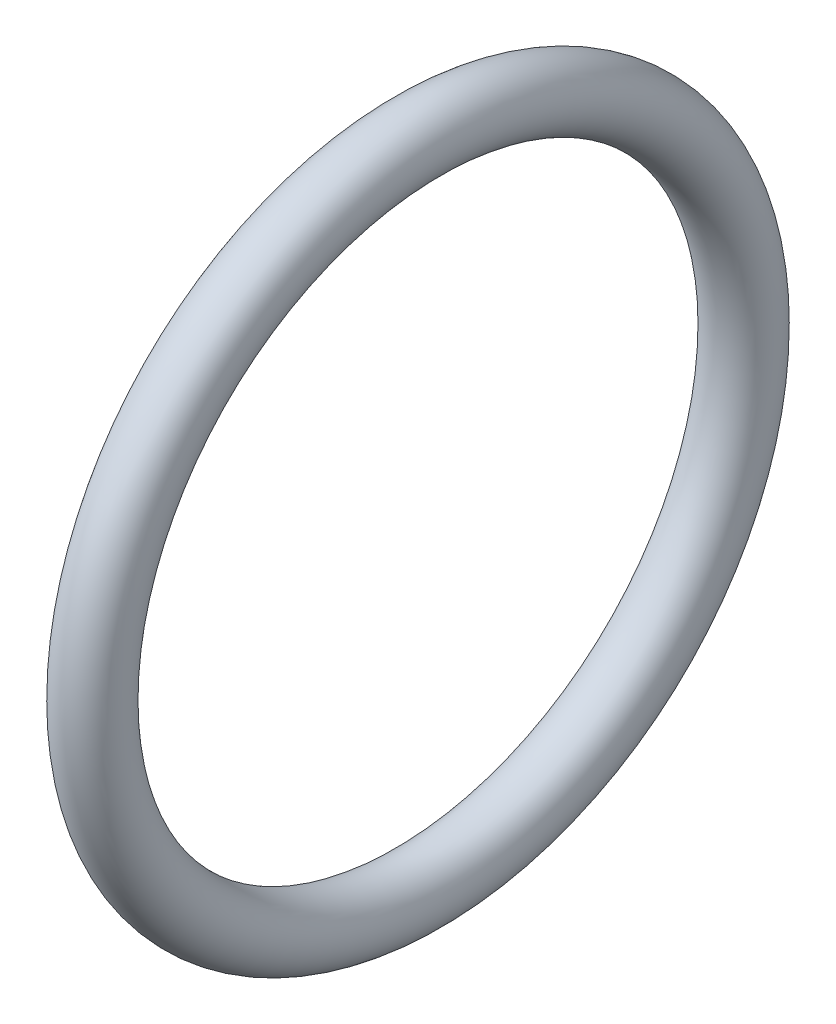
SolidWorks part; units mm, degrees
ref_plane "Plano frontal" through (0, 0, 0) normal (0, 0, 1) x (1, 0, 0)
ref_plane "Plano superior" through (0, 0, 0) normal (0, 1, 0) x (1, 0, 0)
ref_plane "Plano direito" through (0, 0, 0) normal (1, 0, 0) x (0, 0, -1)
sketch "Esboço1" plane through (0, 0, 0) normal (0, 0, 1) x (1, 0, 0)
  line L0 (0, 0) -> (0, 12.1) construction
  line L1 (0, 0) -> (1.6982, 0) construction
  circle A0 centre (0, 12.1) radius 1.2
  dimension "D1" = 2.4
  dimension "D2" = 12.1
revolve "Revolução1" add sketch "Esboço1" angle 360 about L1
ref_axis "Eixo1" through (-1.32, 0, 0) along (1, 0, 0)
